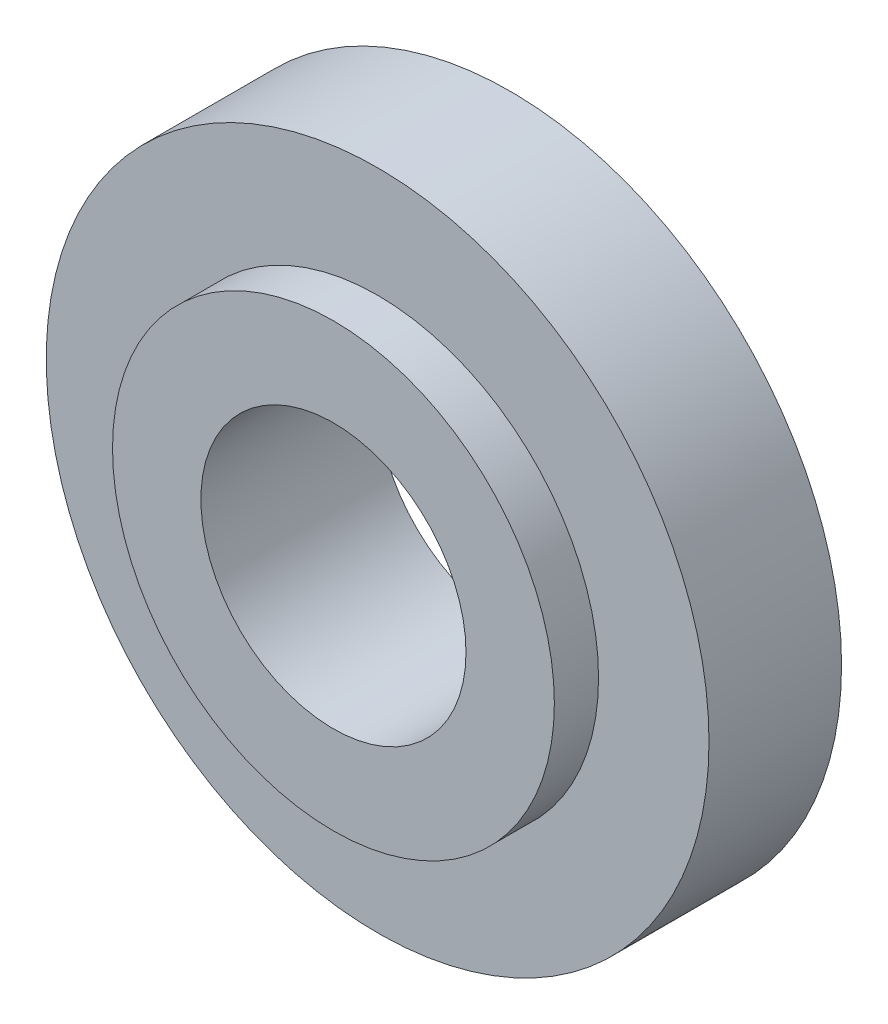
SolidWorks part; units mm, degrees
ref_plane "Front Plane" through (0, 0, 0) normal (0, 0, 1) x (1, 0, 0)
ref_plane "Top Plane" through (0, 0, 0) normal (0, 1, 0) x (1, 0, 0)
ref_plane "Right Plane" through (0, 0, 0) normal (1, 0, 0) x (0, 0, -1)
sketch "Sketch1" plane through (0, 0, 0) normal (0, 0, 1) x (1, 0, 0)
  circle A0 centre (0, 0) radius 7.5
  circle A1 centre (0, 0) radius 5
  circle A2 centre (0, 0) radius 3
  dimension "D1" = 15
  dimension "D2" = 10
  dimension "D3" = 6
extrude "Boss-Extrude1" add sketch "Sketch1" against normal blind 3 contours A0 A1 | A1 A2 region at (-7.2879, 0, 0) region at (-4.8586, 0, 0)
extrude "Boss-Extrude2" add sketch "Sketch1<3>" along normal blind 1 contours A1 A2 region at (-4.8586, 0, 0)
sketch "Sketch1<3>" plane through (0, 0, 0) normal (0, 0, 1) x (1, 0, 0) same geometry as "Sketch1"
